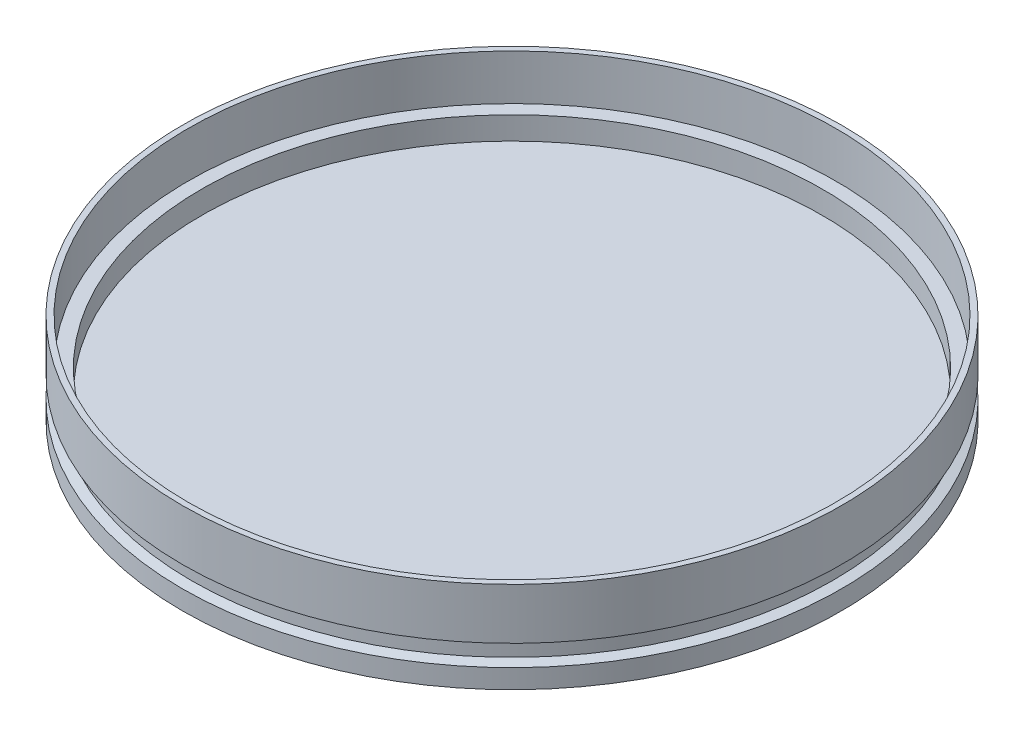
SolidWorks part; units mm, degrees
ref_plane "前基準面" through (0, 0, 0) normal (0, 0, 1) x (1, 0, 0)
ref_plane "上基準面" through (0, 0, 0) normal (0, 1, 0) x (1, 0, 0)
ref_plane "右基準面" through (0, 0, 0) normal (1, 0, 0) x (0, 0, -1)
sketch "草圖1" plane through (0, 0, 0) normal (0, 1, 0) x (1, 0, 0)
  circle A0 centre (0, 0) radius 72.25
  circle A1 centre (0, 0) radius 71
  circle A2 centre (0, 0) radius 68
  circle A3 centre (0, 0) radius 62.25
  dimension "D1" = 144.5
  dimension "D2" = 142
  dimension "D3" = 3
  dimension "D4" = 10
extrude "填料-伸長1" add sketch "草圖1" along normal blind 20 contours A0 A1 region at (-72.0456, 0, 0)
extrude "填料-伸長3" add sketch "草圖1<6>" along normal blind 10 contours A1 A2 region at (-68.9918, 0, 0)
sketch "草圖1<6>" plane through (0, 0, 0) normal (0, 1, 0) x (1, 0, 0) same geometry as "草圖1"
sketch "草圖2" plane through (0, 0, 0) normal (0, 0, 1) x (1, 0, 0)
  line L0 (72.25, 0) -> (72.25, 20) construction
  line L1 (70.25, 8) -> (72.25, 8)
  line L2 (70.25, 8) -> (70.25, 5)
  line L3 (70.25, 5) -> (72.25, 5)
  line L4 (72.25, 8) -> (72.25, 5)
  line L5 (70.25, 8) -> (72.25, 5) construction
  line L6 (70.25, 5) -> (72.25, 8) construction
  line L7 (72.25, 0) -> (-72.25, 0) construction
  line L8 (0, 0) -> (0, 55.3081) construction
  point P0 (71.25, 6.5)
  dimension "D1" = 2
  dimension "D2" = 3
  dimension "D3" = 5
revolve "除料-旋轉1" cut sketch "草圖2" angle 360 about L8
chamfer "導角1" distance 3 angle 15 1 edges at (0, 8, -72.25) first distance on face at (0, 8, -70.25)
chamfer "導角2" distance 3 angle 15 1 edges at (0, 5, -72.25) first distance on face at (0, 5, -72.25)
extrude "填料-伸長5" add sketch "草圖1<8>" along normal blind 5 contours A2 A3 | A3 region at (-66.0767, 0, 0) region at (0, 0, 0)
sketch "草圖1<8>" plane through (0, 0, 0) normal (0, 1, 0) x (1, 0, 0) same geometry as "草圖1"
sketch "草圖5" plane through (0, 0, 0) normal (0, 1, 0) x (1, 0, 0)
  line L1 (-60, 5.5) -> (60, 5.5)
  line L2 (-60, 5.5) -> (-60, -5.5)
  line L3 (-60, -5.5) -> (60, -5.5)
  line L4 (60, 5.5) -> (60, -5.5)
  line L5 (-60, 5.5) -> (60, -5.5) construction
  line L6 (-60, -5.5) -> (60, 5.5) construction
  point P0 (0, 0)
  point P5 (0, 0)
  dimension "D1" = 11
  dimension "D2" = 120
sketch "草圖6" plane through (0, 0, 0) normal (0, 1, 0) x (1, 0, 0)
  line L1 (-16.938, 29.3173) -> (-0.938, 29.3173)
  line L2 (-16.938, 29.3173) -> (-16.938, 17.1173)
  line L3 (-16.938, 17.1173) -> (-0.938, 17.1173)
  line L4 (-0.938, 29.3173) -> (-0.938, 17.1173)
  line L5 (-16.938, 29.3173) -> (-0.938, 17.1173) construction
  line L6 (-16.938, 17.1173) -> (-0.938, 29.3173) construction
  line L7 (-17.938, 30.3173) -> (0.062, 30.3173)
  line L8 (-17.938, 30.3173) -> (-17.938, 16.1173)
  line L9 (-17.938, 16.1173) -> (0.062, 16.1173)
  line L10 (0.062, 30.3173) -> (0.062, 16.1173)
  line L11 (-17.938, 30.3173) -> (0.062, 16.1173) construction
  line L12 (-17.938, 16.1173) -> (0.062, 30.3173) construction
  point P0 (-8.938, 23.2173)
  point P5 (-8.938, 23.2173)
  dimension "D1" = 16
  dimension "D2" = 12.2
  dimension "D3" = 1
  dimension "D4" = 1
  dimension "D5" = 1
  dimension "D6" = 1
